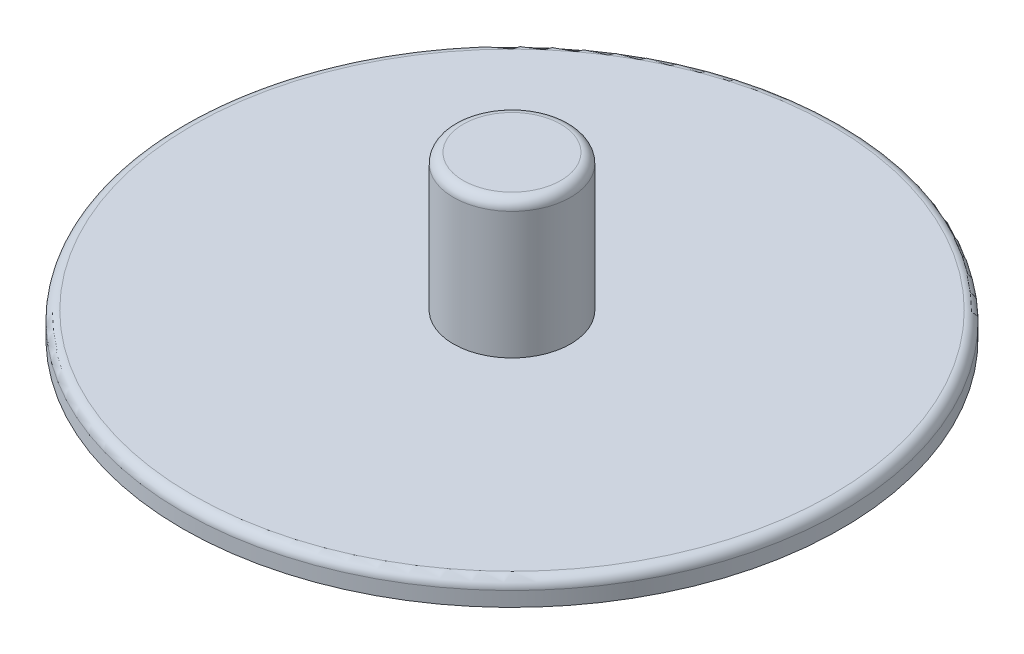
SolidWorks part; units mm, degrees
ref_plane "Front Plane" through (0, 0, 0) normal (0, 0, 1) x (1, 0, 0)
ref_plane "Top Plane" through (0, 0, 0) normal (0, 1, 0) x (1, 0, 0)
ref_plane "Right Plane" through (0, 0, 0) normal (1, 0, 0) x (0, 0, -1)
sketch "Sketch1" plane through (0, 0, 0) normal (0, 1, 0) x (1, 0, 0)
  circle A0 centre (0, 0) radius 85.725
  dimension "D2" = 171.45
extrude "Boss-Extrude1" add sketch "Sketch1" along normal blind 6.35
sketch "Sketch2" plane through (0, 6.35, 0) normal (0, 1, 0) x (1, 0, 0)
  circle A0 centre (0, 0) radius 15.24
  dimension "D1" = 30.48
extrude "Boss-Extrude2" add sketch "Sketch2" along normal blind 35.56
fillet "Fillet1" radius 2.54 1 edges at (0, 41.91, 15.24)
fillet "Fillet2" radius 2.54 1 edges at (0, 6.35, 85.725)
